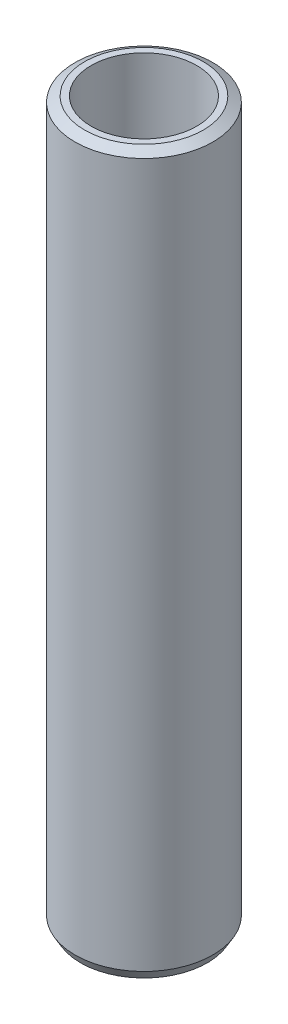
SolidWorks part; units mm, degrees
ref_plane "Front Plane" through (0, 0, 0) normal (0, 0, 1) x (1, 0, 0)
ref_plane "Top Plane" through (0, 0, 0) normal (0, 1, 0) x (1, 0, 0)
ref_plane "Right Plane" through (0, 0, 0) normal (1, 0, 0) x (0, 0, -1)
sketch "Sketch1" plane through (0, 0, 0) normal (0, 1, 0) x (1, 0, 0)
  circle A0 centre (0, 0) radius 57.5
  dimension "SHAFT_OD" = 115
extrude "Boss-Extrude1" add sketch "Sketch1" along normal blind 600
sketch "Sketch2" plane through (0, 0, 0) normal (0, 1, 0) x (1, 0, 0)
  circle A0 centre (0, 0) radius 44.0033
  dimension "BORE_D" = 88.0067
extrude "Cut-Extrude1" cut sketch "Sketch2" along normal through all
chamfer "Chamfer1" distance 4.626 angle 60 2 edges at (0, 600, 57.5) (0, 0, 57.5) first distance on face at (0, 600, 57.5) first distance on face at (0, 0, 44.0033)
